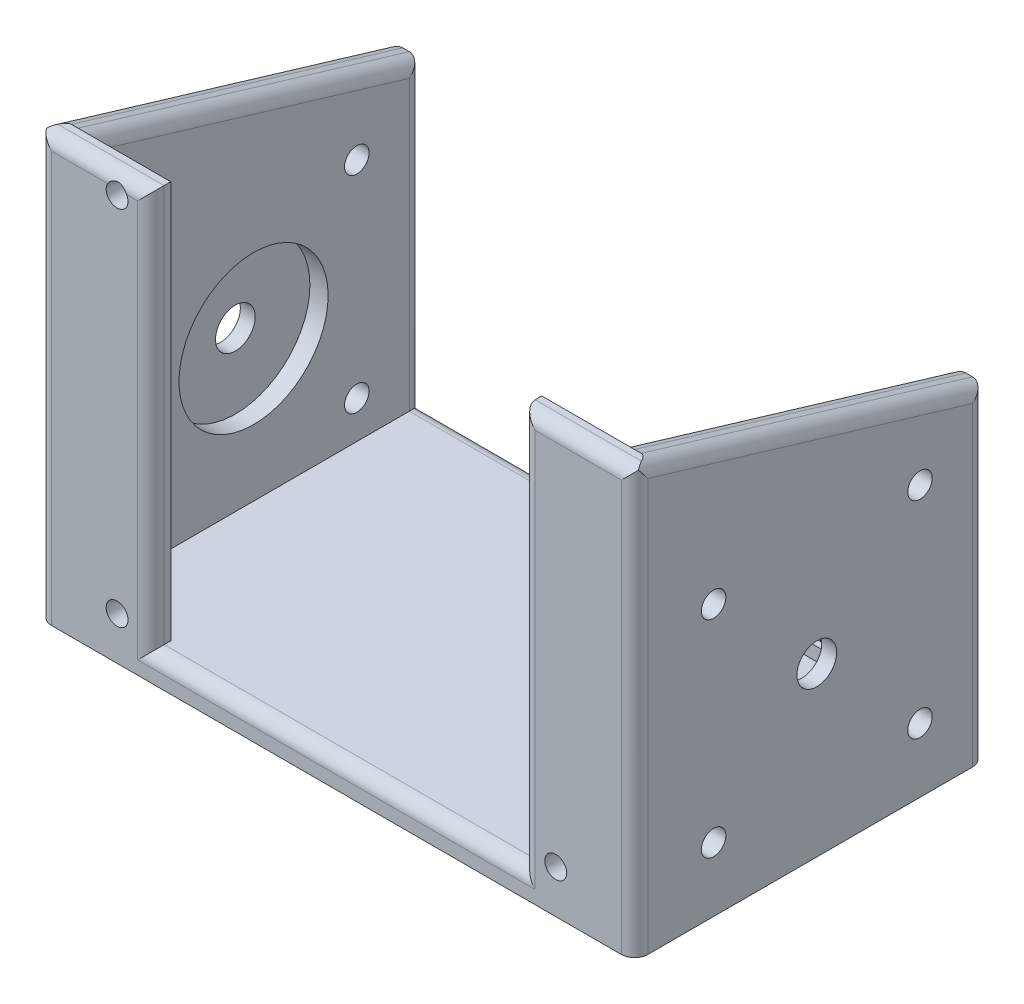
SolidWorks part; units mm, degrees
ref_plane "Plan de face" through (0, 0, 0) normal (0, 0, 1) x (1, 0, 0)
ref_plane "Plan de dessus" through (0, 0, 0) normal (0, 1, 0) x (1, 0, 0)
ref_plane "Plan de droite" through (0, 0, 0) normal (1, 0, 0) x (0, 0, -1)
sketch "Esquisse1" plane through (0, 0, 0) normal (0, 1, 0) x (1, 0, 0)
  line L1 (0, 0) -> (90, 0)
  line L2 (0, 0) -> (0, 53)
  line L3 (0, 53) -> (90, 53)
  line L4 (90, 0) -> (90, 53)
  dimension "D1" = 90
  dimension "D2" = 53
extrude "Boss.-Extru.1" add sketch "Esquisse1" along normal blind 4
sketch "Esquisse2" plane through (0, 4, 0) normal (0, 1, 0) x (1, 0, 0)
  line L2 (0, 53) -> (0, 0)
  line L6 (5, 53) -> (5, 3)
  line L13 (0, 0) -> (90, 0) construction
  line L14 (17, 0) -> (0, 0)
  line L17 (17, 0) -> (17, 3)
  line L18 (17, 3) -> (5, 3)
  line L19 (90, 53) -> (0, 53) construction
  line L20 (0, 53) -> (5, 53)
  dimension "D1" = 12
  dimension "D3" = 5
  dimension "D5" = 3
extrude "Boss.-Extru.2" add sketch "Esquisse2" along normal blind 60
sketch "Esquisse4" plane through (0, 0, 0) normal (-1, 0, 0) x (0, 0, 1)
  line L0 (-43.075, 40.825) -> (-11.925, 9.675) construction
  line L1 (-43.075, 9.675) -> (-11.925, 9.675) construction
  line L2 (-43.075, 9.675) -> (-43.075, 40.825) construction
  line L3 (-43.075, 40.825) -> (-11.925, 40.825) construction
  line L4 (-11.925, 9.675) -> (-11.925, 40.825) construction
  line L5 (-43.075, 9.675) -> (-11.925, 40.825) construction
  line L8 (-53, 0) -> (0, 0) construction
  line L10 (-53, 64) -> (-53, 0) construction
  circle A0 centre (-27.5, 25.25) radius 3
  circle A1 centre (-43.075, 40.825) radius 1.85
  circle A2 centre (-11.925, 40.825) radius 1.85
  circle A3 centre (-11.925, 9.675) radius 1.85
  circle A4 centre (-43.075, 9.675) radius 1.85
  point P10 (-27.5, 25.25)
  dimension "D2" = 3.7
  dimension "D5" = 6
  dimension "D1" = 31.15
  dimension "D3" = 25.5
  dimension "D4" = 25.25
extrude "Enlèv. mat.-Extru.1" cut sketch "Esquisse4" against normal up to next and the other way through all
sketch "Esquisse5" plane through (5, 0, 0) normal (1, 0, 0) x (0, 0, -1)
  circle A0 centre (27.5, 25.25) radius 11.25
  dimension "D1" = 22.5
extrude "Enlèv. mat.-Extru.2" cut sketch "Esquisse5" against normal blind 2.75
ref_point "Point1"
ref_axis "Axe2" through (45, 0, 0) along (0, 1, 0)
ref_plane "Plan de sym" through (45, 0, 0) normal (1, 0, 0) x (0, 0, -1)
sketch "Esquisse9" plane through (0, 0, 0) normal (-1, 0, 0) x (0, 0, 1)
  line L0 (-53, 49) -> (-3, 64)
  line L1 (-53, 64) -> (-53, 0) construction
  line L2 (-53, 64) -> (0, 64) construction
  line L3 (-3, 64) -> (-53, 64)
  line L4 (-53, 64) -> (-53, 49)
  dimension "D1" = 15
  dimension "D2" = 50
extrude "Enlèv. mat.-Extru.5" cut sketch "Esquisse9" against normal up to next
mirror "Symétrie1" about plane through (45, 0, 0) normal (1, 0, 0) of "Enlèv. mat.-Extru.5", "Enlèv. mat.-Extru.2", "Enlèv. mat.-Extru.1", "Boss.-Extru.2"
sketch "Esquisse6" plane through (0, 0, 0) normal (0, 0, 1) x (1, 0, 0)
  line L0 (45, -29.15) -> (45, 29.15) construction
  line L1 (0, 0) -> (90, 0) construction
  circle A0 centre (11.8997, 6.5) radius 1.65
  circle A1 centre (11.8997, 61.1701) radius 1.65
  circle A2 centre (78.1002, 6.5) radius 1.65
  dimension "D1" = 3.3
  dimension "D2" = 66.2005
  dimension "D3" = 33.1003
  dimension "D4" = 54.6701
  dimension "D5" = 6.5
extrude "Enlèv. mat.-Extru.3" cut sketch "Esquisse6" against normal up to next
sketch "Esquisse7" plane through (0, 0, -53) normal (0, 0, -1) x (-1, 0, 0)
  line L0 (-85, 4) -> (-85, 24)
  line L1 (-85, 64) -> (-85, 4) construction
  line L2 (-85, 24) -> (-83, 24)
  line L3 (-83, 24) -> (-83, 6)
  line L4 (-83, 6) -> (-36, 6)
  line L5 (-36, 6) -> (-36, 4)
  line L6 (-85, 4) -> (-5, 4) construction
  line L7 (-36, 4) -> (-85, 4)
  dimension "D1" = 2
  dimension "D2" = 49
  dimension "D3" = 20
extrude "Boss.-Extru.3" add sketch "Esquisse7" against normal blind 4
sketch "Esquisse8" plane through (0, 6, 0) normal (0, 1, 0) x (1, 0, 0)
  line L0 (50.0791, 52.075) -> (50.0791, 53) construction
  line L1 (38, 52.075) -> (84.15, 52.075)
  line L2 (38, 52.075) -> (38, 49.925)
  line L3 (38, 49.925) -> (84.15, 49.925)
  line L4 (84.15, 52.075) -> (84.15, 49.925)
  line L5 (36, 53) -> (83, 53) construction
  line L6 (50.0791, 49.925) -> (50.0791, 49) construction
  line L7 (36, 49) -> (83, 49) construction
  line L8 (83, 49) -> (83, 53) construction
  line L11 (36, 49) -> (36, 53) construction
  dimension "D1" = 2.15
  dimension "D2" = 1.15
  dimension "D3" = 2
extrude "Enlèv. mat.-Extru.4" cut sketch "Esquisse8" against normal blind 2 and the other way up to next
sketch "Esquisse10" plane through (0, 0, -53) normal (0, 0, 1) x (1, 0, 0)
  line L0 (0, 0) -> (90, 0) construction
  line L1 (37.5, 0) -> (52.5, 0)
  line L2 (37.5, 0) -> (37.5, 4)
  line L3 (37.5, 4) -> (52.5, 4)
  line L4 (52.5, 0) -> (52.5, 4)
  line L5 (85, 4) -> (36, 4) construction
  line L6 (45, 0) -> (45, 33.0561) construction
  dimension "D1" = 15
  dimension "D2" = 7.5
extrude "Boss.-Extru.4" add sketch "Esquisse10" against normal blind 20
fillet "Congé2" radius 2 19 edges at (85, 36.5, -53) (45, 4, 0) (5, 56.5, -28) (85, 56.5, -28) (73, 34, 0) (17, 34, 0) (0, 24.5, -53) (5, 26.5, -53) (20.5, 4, -53) (90, 24.5, -53) (90, 32, 0) (90, 56.5, -28) (81.5, 64, 0) (8.5, 64, 0) (0, 56.5, -28) (0, 32, 0) (52.5, 4, -63) (45, 4, -73) (37.5, 4, -63)
sketch "Esquisse11" plane through (0, 4, 0) normal (0, 1, 0) x (1, 0, 0)
  line L3 (45, -28.05) -> (45, 28.05) construction
  line L4 (50.5, 53) -> (39.5, 53) construction
  circle A0 centre (45, 55.5) radius 1.11
  circle A1 centre (45, 69) radius 1.11
  point P4 (44.8797, -5.3252)
  point P5 (44.8797, -13.6908)
  point P6 (0, 0)
  point P7 (45, 68.4579)
  point P11 (0, 0)
  dimension "D1" = 2.22
  dimension "D2" = 13.5
  dimension "D3" = 2.5
extrude "Enlèv. mat.-Extru.6" cut sketch "Esquisse11" against normal up to next
equation "\"D3@Esquisse6\"=\"D2@Esquisse6\"/2"
equation "\"D2@Esquisse10\"=\"D1@Esquisse10\"/2"
